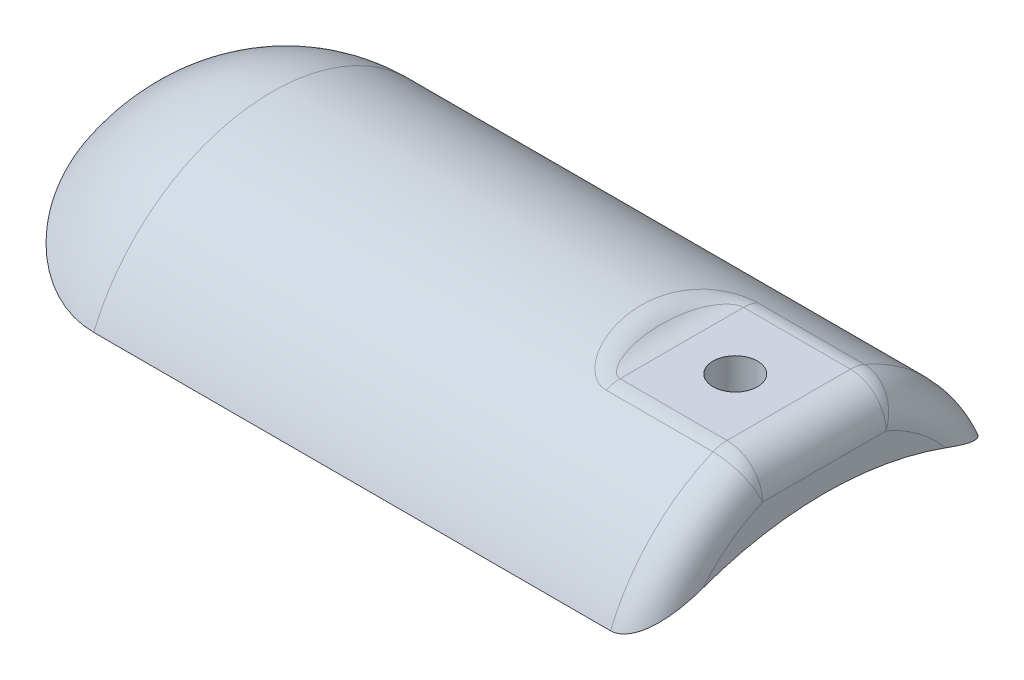
SolidWorks part; units mm, degrees
material "Acrylic (Medium-high impact)"
ref_plane "Front Plane" through (0, 0, 0) normal (0, 0, 1) x (1, 0, 0)
ref_plane "Top Plane" through (0, 0, 0) normal (0, 1, 0) x (1, 0, 0)
ref_plane "Right Plane" through (0, 0, 0) normal (1, 0, 0) x (0, 0, -1)
sketch "Sketch2" plane through (0, 0, 0) normal (1, 0, 0) x (0, 0, -1)
  line L0 (-12.7, 0) -> (12.7, 0) construction
  arc A0 (-12.7, 0) -> (12.7, 0) centre (0, -21.997) cw
  arc A1 (-12.7, 0) -> (12.7, 0) centre (0, -5.2402) cw
  dimension "D1" = 25.4
  dimension "D2" = 25.4
extrude "Boss-Extrude1" add sketch "Sketch2" along normal blind 50.8
sketch "Sketch3" plane through (50.8, 0, 0) normal (1, 0, 0) x (0, 0, -1)
  line L1 (4.8913, 7.5982) -> (-4.8913, 7.5982)
  line L2 (4.8913, 7.5982) -> (4.8913, 8.4984)
  line L3 (4.8913, 8.4984) -> (-4.8913, 8.4984)
  line L4 (-4.8913, 7.5982) -> (-4.8913, 8.4984)
  arc A0 (12.7, 0) -> (-12.7, 0) centre (0, -5.2402) ccw construction
  point P4 (0, 8.4984)
extrude "Cut-Extrude1" cut sketch "Sketch3" against normal blind 12.7
fillet "Fillet1" radius 2.54 1 edges at (38.1, 7.5982, 0)
fillet "Fillet3" radius 2.54 6 edges at (38.7002, 8.4984, 0) (50.8, 4.6063, 9.5811) (50.8, 7.5982, 0) (50.8, 4.6063, -9.5811) (45.72, 7.5982, -4.8913) (45.72, 7.5982, 4.8913)
sketch "Sketch4" plane through (0, 7.5982, 0) normal (0, 1, 0) x (1, 0, 0)
  line L0 (40.64, 4.3991) -> (44.45, 0) construction
  line L1 (44.45, 0) -> (48.26, -4.3991) construction
  circle A0 centre (44.45, 0) radius 1.5875
  dimension "D1" = 3.175
extrude "Cut-Extrude2" cut sketch "Sketch4" against normal through all
fillet "Fillet4" radius 11.43 1 edges at (0, 8.4984, 0)
